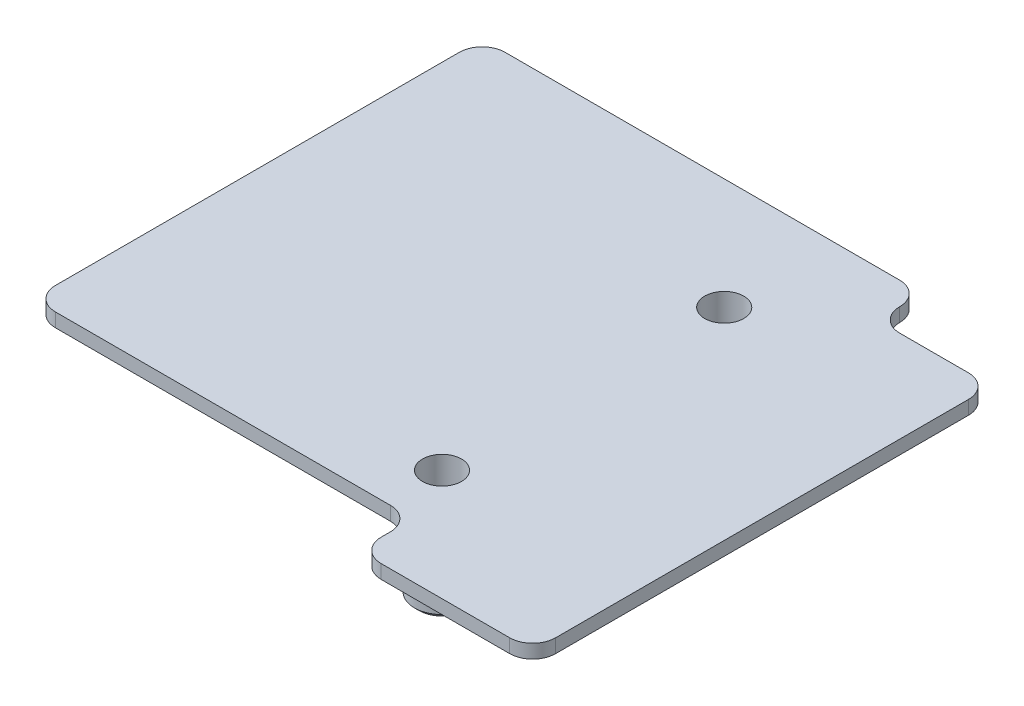
SolidWorks part; units mm, degrees
ref_plane "Front Plane" through (0, 0, 0) normal (0, 0, 1) x (1, 0, 0)
ref_plane "Top Plane" through (0, 0, 0) normal (0, 1, 0) x (1, 0, 0)
ref_plane "Right Plane" through (0, 0, 0) normal (1, 0, 0) x (0, 0, -1)
sketch "Sketch1" plane through (0, 0, 0) normal (0, 1, 0) x (1, 0, 0)
  line L0 (0, 0) -> (83, 0)
  line L1 (83, 0) -> (83, -12)
  line L2 (83, -12) -> (121, -12)
  line L3 (121, -12) -> (121, 88)
  line L5 (0, 98) -> (0, 0)
  line L6 (0, 43) -> (121, 43) construction
  line L7 (77, 73.75) -> (77, 12.25) construction
  line L8 (0, 98) -> (96, 98)
  line L9 (96, 98) -> (96, 88)
  line L10 (96, 88) -> (121, 88)
  line L11 (86.8502, -12) -> (86.8502, 98) construction
  point P11 (77, 43)
  point P13 (77, 73.75)
  point P14 (77, 12.25)
  point P18 (86.8502, 43)
  dimension "D1" = 121
  dimension "D2" = 110
  dimension "D3" = 38
  dimension "D4" = 12
  dimension "D5" = 61.5
  dimension "D6" = 44
  dimension "D7" = 10
  dimension "D8" = 25
extrude "plate" add sketch "Sketch1" along normal blind 3
sketch "Sketch2" plane through (0, 0, 0) normal (0, 1, 0) x (1, 0, 0)
  circle A0 centre (77, 73.75) radius 6
  circle A1 centre (77, 12.25) radius 6
  dimension "D1" = 12
extrude "mount posts" add sketch "Sketch2" against normal blind 21
sketch "Sketch3" plane through (0, 3, 0) normal (0, 1, 0) x (1, 0, 0)
  circle A0 centre (77, 73.75) radius 4.25
  circle A1 centre (77, 12.25) radius 4.25
  dimension "D1" = 8.5
extrude "mount cbore" cut sketch "Sketch3" against normal offset from surface (20 mm away) 4 up to face at (77, -21, -67.75)
hole_wizard "#8 Clearance Hole1" positions "Sketch4" profile "Sketch5" hole size "#8" standard "ANSI Inch" end condition through all
sketch "Sketch4" plane through (0, -17, 0) normal (0, 1, 0) x (1, 0, 0)
  circle A0 centre (77, 12.25) radius 4.25 construction
  circle A1 centre (77, 73.75) radius 4.25 construction
  point P0 (77, 73.75)
  point P2 (77, 12.25)
sketch "Sketch5" plane through (77, -17, -73.75) normal (1, 0, 0) x (0, 0, 1)
  line L0 (0, 0) -> (0, 4)
  line L1 (0, 4) -> (2.2479, 4)
  line L2 (2.2479, 4) -> (2.2479, 0)
  line L5 (2.2479, 0) -> (0, 0)
  line L11 (0, -6.35) -> (0, 107.95) construction
  dimension "Thru Hole Dia." = 4.4958
  dimension "Thru Hole Depth" = 4
ref_plane "mid plane" through (0, 0, -43) normal (0, 0, -1) x (1, 0, 0)
sketch "Sketch8" plane through (0, 0, -43) normal (0, 0, -1) x (1, 0, 0)
  line L0 (47.25, 0) -> (48.85, 0)
  line L1 (0, 0) -> (121, 0) construction
  line L2 (47.25, 0) -> (45.5, 29)
  line L3 (45.5, 29) -> (47.1, 29)
  line L4 (47.1, 29) -> (48.85, 0)
  line L5 (42, 0) -> (42, 41.9178) construction
  line L6 (81.4832, 21) -> (59.4094, 21) construction
  line L8 (83, 21) -> (71, 21) construction
  dimension "D1" = 1.6
  dimension "D2" = 3.5
  dimension "D3" = 8
  dimension "D4" = 5.25
  dimension "D5" = 42
revolve "foot" add sketch "Sketch8" angle 360 about L5
fillet "Fillet1" radius 1.5 2 edges at (42, 0, -37.75) (42, 0, -36.15)
sketch "Sketch7" plane through (0, 3, 0) normal (0, 1, 0) x (1, 0, 0)
  line L0 (107.15, 87.7375) -> (107.15, 106.2625) construction
  line L1 (121, -12) -> (121, 88) construction
  line L2 (83, -12) -> (121, -12) construction
  line L3 (115, 18.85) -> (99.3, 18.85) construction
  line L4 (102.65, 9.325) -> (102.65, 28.375)
  line L5 (99.3, -6) -> (99.3, 43.7) construction
  line L6 (99.3, -6) -> (115, -6) construction
  line L7 (115, -6) -> (115, 43.7) construction
  line L8 (99.3, 43.7) -> (115, 43.7) construction
  line L9 (99.3, -6) -> (115, 43.7) construction
  line L10 (115, -6) -> (99.3, 43.7) construction
  line L11 (111.65, 9.325) -> (111.65, 28.375)
  circle A0 centre (107.15, 9.325) radius 4.5 construction
  circle A1 centre (107.15, 28.375) radius 4.5 construction
  arc A2 (102.65, 9.325) -> (111.65, 9.325) centre (107.15, 9.325) ccw
  arc A3 (102.65, 28.375) -> (111.65, 28.375) centre (107.15, 28.375) cw
  circle A4 centre (107.15, 37.9) radius 1.9
  circle A5 centre (107.15, -0.2) radius 1.9
  point P16 (107.15, 18.85)
  point P19 (102, -12)
  dimension "D2" = 19.05
  dimension "D5" = 9
  dimension "D6" = 3.8
  dimension "D1" = 49.7
  dimension "D3" = 6
  dimension "D4" = 15.7
  dimension "D7" = 38.1
  dimension "D8" = 6
extrude "terminal strip" [suppressed] cut sketch "Sketch7" against normal through all
chamfer "Chamfer1" distance 3 angle 45 2 edges at (77, -17, -69.5) (77, -17, -8)
chamfer "Chamfer2" distance 1 angle 45 2 edges at (77, -21, -6.25) (77, -21, -67.75)
fillet "Fillet3" radius 1.5 2 edges at (77, 0, -67.75) (77, 0, -6.25)
fillet "corners" radius 5 8 edges at (0, 1.5, -98) (96, 1.5, -98) (96, 1.5, -88) (121, 1.5, -88) (121, 1.5, 12) (83, 1.5, 12) (83, 1.5, 0) (0, 1.5, 0)
